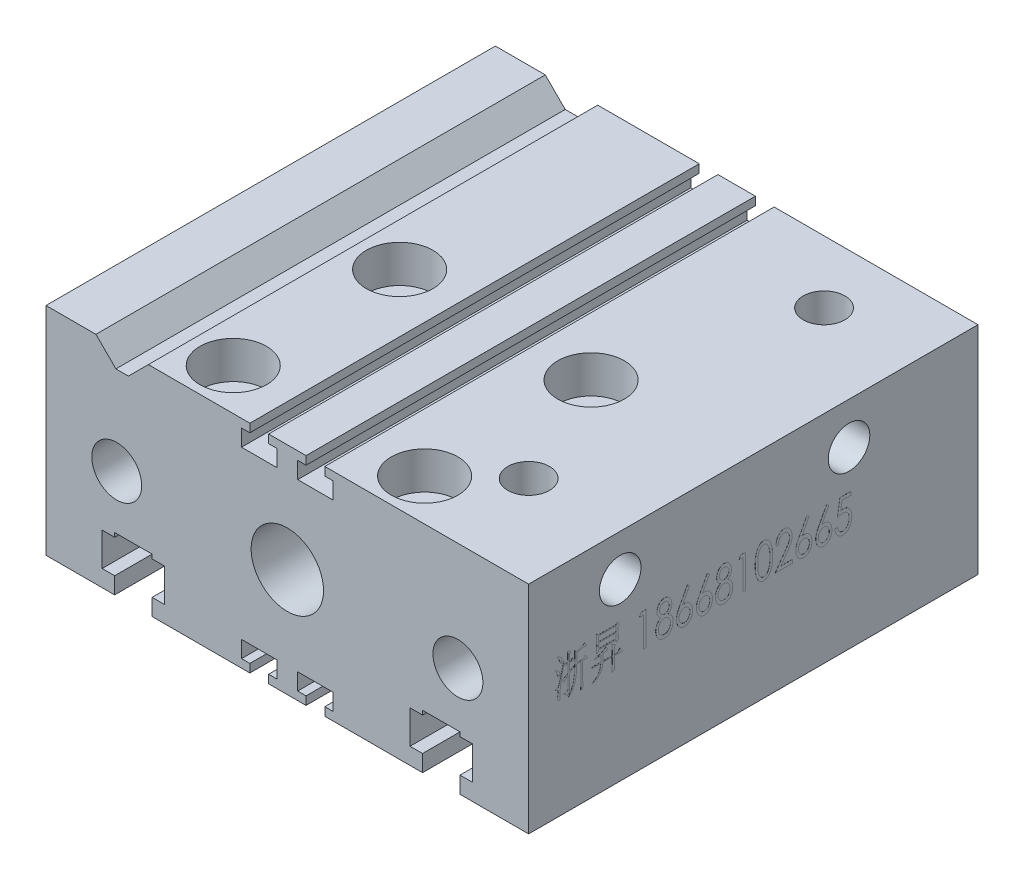
SolidWorks part; units mm, degrees
ref_plane "前视基准面" through (0, 0, 0) normal (0, 0, 1) x (1, 0, 0)
ref_plane "上视基准面" through (0, 0, 0) normal (0, 1, 0) x (1, 0, 0)
ref_plane "右视基准面" through (0, 0, 0) normal (1, 0, 0) x (0, 0, -1)
sketch "草图1" plane through (0, 0, 0) normal (0, 1, 0) x (1, 0, 0)
  line L0 (0, 0) -> (0, 54) construction
  line L1 (-29, 54) -> (29, 54)
  line L2 (-29, 54) -> (-29, 0)
  line L3 (-29, 0) -> (29, 0)
  line L4 (29, 54) -> (29, 0)
  line L5 (-11.5, 0) -> (-11.5, 54) construction
  line L6 (18, 54) -> (18, 0) construction
  line L7 (4.35, 0) -> (4.35, -5)
  line L8 (-29, -5) -> (29, -5)
  line L9 (-29, -5) -> (-29, -13)
  line L10 (-29, -13) -> (29, -13)
  line L11 (29, -5) -> (29, -13)
  line L12 (29, 0) -> (71, 0)
  circle A0 centre (18, 46.5) radius 2.5
  point P4 (29, 25)
  point P8 (0, 25)
  point P11 (-11.5, 5)
  point P12 (-11.5, 25)
  point P15 (18, 46.5)
  point P16 (18, 11)
  point P19 (29, 11)
  point P20 (29, 13.5)
  point P21 (29, 38.5)
  point P28 (0, 51)
  point P29 (0, 48)
  point P30 (-11.5, 15)
  point P31 (18, 54)
  point P33 (-11.5, 44)
  dimension "D2" = 38.5
  dimension "P" = 5
  dimension "D1" = 54
  dimension "B" = 58
  dimension "AC" = 29
  dimension "行程" = 25
  dimension "KB" = 23
  dimension "MB" = 5
  dimension "MC" = 20
  dimension "PB" = 18
  dimension "PD" = 11
  dimension "PF" = 7.5
  dimension "PC" = 11
  dimension "PE" = 13.5
  dimension "D3" = 8.7
  dimension "AD" = 8
  dimension "AB" = 13
  dimension "D4" = 67
  dimension "JA" = 3
  dimension "KA" = 6
  dimension "KC" = 15
  dimension "A" = 42
  dimension "LA" = 10
sketch "草图2" plane through (0, 0, 0) normal (0, 0, 1) x (1, 0, 0)
  line L0 (-29, 0) -> (0, 0) construction
  line L1 (-29, 13) -> (29, 13)
  line L2 (-29, 13) -> (-29, -13)
  line L3 (-29, -13) -> (-20.75, -13)
  line L4 (29, 13) -> (29, -13)
  line L5 (-29, 0) -> (29, 0) construction
  line L6 (0, 0) -> (0, 13) construction
  line L7 (-11.5, 13) -> (-11.5, -13) construction
  line L8 (-7.5, 13) -> (-7.5, 8.5)
  line L9 (-7.5, 8.5) -> (-9.25, 8.5)
  line L10 (-9.25, 8.5) -> (-9.25, -13)
  line L11 (29, 8) -> (24, 8)
  line L12 (-29, 0) -> (29, 0) construction
  line L13 (-11.75, 0) -> (-11.25, 0) construction
  line L14 (-11.75, 1.5) -> (-11.25, 1.5)
  line L15 (-11.75, -1.5) -> (-11.25, -1.5)
  line L16 (-9.25, -3) -> (-9, -3)
  line L17 (-2.25, -13) -> (-2.25, -12)
  line L18 (-9, -3) -> (-9, -13)
  line L19 (-4.5, -12) -> (-4.5, -13)
  line L20 (-16.25, -13) -> (-16.25, -11)
  line L21 (-16.25, -11) -> (-14.75, -11)
  line L22 (-14.75, -11) -> (-14.75, -7)
  line L23 (-14.75, -7) -> (-16.25, -7)
  line L24 (-22.25, -7) -> (-22.25, -11)
  line L25 (-22.25, -11) -> (-20.75, -11)
  line L26 (-20.75, -11) -> (-20.75, -13)
  line L27 (-23, 13) -> (-20.6, 10.6)
  line L28 (-20.6, 10.6) -> (-19.1, 10.6)
  line L29 (-19.1, 10.6) -> (-16.7, 13)
  line L36 (-20.75, -7) -> (-22.25, -7)
  line L37 (-20.75, -6.5) -> (-16.25, -6.5)
  line L38 (-20.75, -6.5) -> (-20.75, -7)
  line L39 (-16.25, -13) -> (29, -13)
  line L40 (-16.25, -6.5) -> (-16.25, -7)
  line L41 (-20.75, -13) -> (-16.25, -13) construction
  line L42 (-2.25, -12) -> (-1.25, -12)
  line L43 (-5.5, -10) -> (-1.25, -10)
  line L44 (-5.5, -10) -> (-5.5, -12)
  line L45 (-5.5, -12) -> (-4.5, -12)
  line L46 (-1.25, -10) -> (-1.25, -12)
  circle A0 centre (-20.5, 0) radius 3
  circle A1 centre (20.5, 0) radius 3
  circle A2 centre (-25, 9) radius 2
  circle A3 centre (-25, -9) radius 2
  circle A4 centre (11.5, 0) radius 1.5
  arc A5 (-11.75, 1.5) -> (-11.75, -1.5) centre (-11.75, 0) ccw
  arc A6 (-11.25, -1.5) -> (-11.25, 1.5) centre (-11.25, 0) ccw
  point P48 (-11.5, 0)
  point P52 (-18.5, -13)
  point P64 (-9.75, 0)
  point P65 (-13.25, 0)
  dimension "D1" = 1
  dimension "D" = 6
  dimension "D7" = 10.4
  dimension "L" = 4
  dimension "D10" = 2.4
  dimension "K" = 3
  dimension "C" = 26
  dimension "G" = 41
  dimension "U" = 7.5
  dimension "W" = 4
  dimension "V" = 4.5
  dimension "X" = 2
  dimension "Y" = 6.5
  dimension "S" = 37
  dimension "D2" = 1
  dimension "D3" = 2
  dimension "M" = 8
  dimension "MA" = 4.5
  dimension "N" = 4.5
  dimension "D4" = 2.25
  dimension "D5" = 2
  dimension "D6" = 135
  dimension "LC" = 18
  dimension "LB" = 50
  dimension "D8" = 2
  dimension "D9" = 5
  dimension "PA" = 8
  dimension "J" = 3.5
  dimension "R" = 5
  dimension "RA" = 10
sketch "草图3" plane through (0, 0, 0) normal (0, 0, 1) x (1, 0, 0)
  line L0 (0, 11) -> (0, 0) construction
  line L1 (-28, 11) -> (28, 11)
  line L2 (-28, 11) -> (-28, -11)
  line L3 (-28, -11) -> (28, -11)
  line L4 (28, 11) -> (28, -11)
  line L5 (-29, 0) -> (29, 0) construction
  line L6 (0, 0) -> (0, -11) construction
  line L7 (-29, 0) -> (29, 0) construction
  circle A0 centre (-24, 7) radius 2
  circle A1 centre (-25, 9) radius 2 construction
  dimension "BA" = 56
  dimension "CA" = 22
  dimension "LD" = 48
  dimension "LE" = 14
sketch "草图4" plane through (0, 0, 0) normal (0, 0, 1) x (1, 0, 0)
  line L0 (-14.75, -7) -> (-16.25, -7) construction
  line L1 (-14.75, -11) -> (-14.75, -7) construction
  line L2 (-16.25, -11) -> (-14.75, -11) construction
  line L3 (-16.25, -13) -> (-16.25, -11) construction
  line L4 (-16.25, -13) -> (29, -13) construction
  line L6 (-29, 13) -> (29, 13) construction
  line L7 (-29, 13) -> (-29, -13) construction
  line L8 (-29, -13) -> (-20.75, -13) construction
  line L9 (-20.75, -11) -> (-20.75, -13) construction
  line L10 (-22.25, -11) -> (-20.75, -11) construction
  line L11 (-22.25, -7) -> (-22.25, -11) construction
  line L12 (-20.75, -7) -> (-22.25, -7) construction
  line L13 (-20.75, -6.5) -> (-20.75, -7) construction
  line L14 (-20.75, -6.5) -> (-16.25, -6.5) construction
  line L15 (-16.25, -6.5) -> (-16.25, -7) construction
  line L26 (-23, 13) -> (-20.6, 10.6) construction
  line L27 (-20.6, 10.6) -> (-19.1, 10.6) construction
  line L28 (-19.1, 10.6) -> (-16.7, 13) construction
  line L29 (-14.75, -7) -> (-16.25, -7)
  line L30 (-14.75, -11) -> (-14.75, -7)
  line L31 (-16.25, -11) -> (-14.75, -11)
  line L32 (-16.25, -13) -> (-16.25, -11)
  line L33 (-16.25, -13) -> (0, -13)
  line L35 (-29, 13) -> (-23, 13)
  line L36 (-29, 13) -> (-29, -13)
  line L37 (-29, -13) -> (-20.75, -13)
  line L38 (-20.75, -11) -> (-20.75, -13)
  line L39 (-22.25, -11) -> (-20.75, -11)
  line L40 (-22.25, -7) -> (-22.25, -11)
  line L41 (-20.75, -7) -> (-22.25, -7)
  line L42 (-20.75, -6.5) -> (-20.75, -7)
  line L43 (-20.75, -6.5) -> (-16.25, -6.5)
  line L44 (-16.25, -6.5) -> (-16.25, -7)
  line L45 (0, 13) -> (0, -13)
  line L52 (-16.7, 13) -> (0, 13)
  line L55 (-23, 13) -> (-20.6, 10.6)
  line L56 (-20.6, 10.6) -> (-19.1, 10.6)
  line L57 (-19.1, 10.6) -> (-16.7, 13)
  circle A4 centre (-20.5, 0) radius 3 construction
  circle A5 centre (-20.5, 0) radius 3
extrude "凸台-拉伸1" add sketch "草图4" against normal up to vertex (54 mm away) up to point (0, 0, -54)
sketch "草图5" plane through (0, 0, 0) normal (0, 0, 1) x (1, 0, 0)
  line L0 (-5.5, -12) -> (-4.5, -12) construction
  line L1 (-4.5, -12) -> (-4.5, -13) construction
  line L2 (-5.5, -10) -> (-5.5, -12) construction
  line L3 (-5.5, -10) -> (-1.25, -10) construction
  line L4 (-1.25, -10) -> (-1.25, -12) construction
  line L5 (-2.25, -12) -> (-1.25, -12) construction
  line L6 (-2.25, -13) -> (-2.25, -12) construction
  line L7 (-5.5, -12) -> (-4.5, -12)
  line L8 (-4.5, -12) -> (-4.5, -13)
  line L9 (-5.5, -10) -> (-5.5, -12)
  line L10 (-5.5, -10) -> (-1.25, -10)
  line L11 (-1.25, -10) -> (-1.25, -12)
  line L12 (-2.25, -12) -> (-1.25, -12)
  line L13 (-2.25, -13) -> (-2.25, -12)
  line L14 (-4.5, -13) -> (-2.25, -13)
extrude "切除-拉伸1" cut sketch "草图5" against normal through all
mirror "镜向1" about plane through (0, 0, 0) normal (0, 1, 0) of "切除-拉伸1"
sketch "草图6" plane through (0, 13, 0) normal (0, 1, 0) x (-1, 0, 0)
  circle A0 centre (11.5, -25) radius 4
  circle A1 centre (11.5, -5) radius 4
  point P6 (7.5, -5)
extrude "切除-拉伸2" cut sketch "草图6" against normal up to vertex (4.5 mm away) up to point (-7.5, 8.5, 0)
sketch "草图7" plane through (0, 8.5, 0) normal (0, 1, 0) x (1, 0, 0)
  circle A0 centre (-11.5, 25) radius 2.25
  circle A1 centre (-11.5, 5) radius 2.25
  point P6 (-9.25, 25)
extrude "切除-拉伸3" cut sketch "草图7" against normal up to vertex (21.5 mm away) up to point (-9.25, -13, 0)
mirror "镜向2" about plane through (0, 0, 0) normal (1, 0, 0) of bodies 105
sketch "草图8" plane through (0, 0, 0) normal (0, 0, 1) x (1, 0, 0)
  line L0 (16.7, 13) -> (23, 13)
  line L1 (23, 13) -> (20.6, 10.6)
  line L2 (20.6, 10.6) -> (19.1, 10.6)
  line L3 (19.1, 10.6) -> (16.7, 13)
extrude "凸台-拉伸2" add sketch "草图8" against normal up to surface (54 mm away) up to face at (-17.5, 0, -54)
sketch "草图9" plane through (0, 13, 0) normal (0, 1, 0) x (1, 0, 0)
  circle A0 centre (18, 46.5) radius 2.5
  circle A1 centre (18, 11) radius 2.5
  circle A2 centre (18, 46.5) radius 2.5 construction
extrude "切除-拉伸4" cut sketch "草图9" against normal blind 5
sketch "草图10" plane through (29, 0, 0) normal (1, 0, 0) x (0, 0, -1)
  circle A0 centre (11, 8) radius 2.5
  circle A1 centre (38.5, 8) radius 2.5
  dimension "D1" = 5
extrude "切除-拉伸5" cut sketch "草图10" against normal up to vertex (5 mm away) up to point (24, 8, 0)
sketch "草图11" plane through (0, 0, 0) normal (0, 0, 1) x (1, 0, 0)
  line L0 (-29, 0) -> (29, 0) construction
  circle A0 centre (0, 0) radius 4.35
extrude "切除-拉伸6" cut sketch "草图11" against normal up to vertex (46.5 mm away) up to point (18, 0, -46.5)
sketch "草图12" plane through (0, 0, -54) normal (0, 0, -1) x (-1, 0, 0)
  line L0 (11.75, 1.5) -> (11.25, 1.5) construction
  line L1 (11.75, -1.5) -> (11.25, -1.5) construction
  line L2 (11.75, 1.5) -> (11.25, 1.5)
  line L3 (11.75, -1.5) -> (11.25, -1.5)
  circle A0 centre (-11.5, 0) radius 1.5 construction
  arc A1 (11.75, -1.5) -> (11.75, 1.5) centre (11.75, 0) ccw construction
  arc A2 (11.25, 1.5) -> (11.25, -1.5) centre (11.25, 0) ccw construction
  circle A3 centre (-11.5, 0) radius 1.5
  arc A4 (11.75, -1.5) -> (11.75, 1.5) centre (11.75, 0) ccw
  arc A5 (11.25, 1.5) -> (11.25, -1.5) centre (11.25, 0) ccw
extrude "切除-拉伸7" cut sketch "草图12" against normal up to vertex (3 mm away) up to point (0, 0, -51)
sketch "草图13" plane through (0, 0, -51) normal (0, 0, -1) x (-1, 0, 0)
  line L0 (11.5, 13) -> (11.5, -13) construction
  circle A0 centre (11.5, 0) radius 1.5
  circle A2 centre (-11.5, 0) radius 1.5
  circle A3 centre (-11.5, 0) radius 1.5
  dimension "D1" = 0
extrude "凸台-拉伸4" add sketch "草图13" against normal up to vertex (3 mm away) up to point (0, 0, -48)
sketch "草图14" plane through (0, -13, 0) normal (0, -1, 0) x (1, 0, 0)
  circle A0 centre (-11.5, -15) radius 1.5
  circle A1 centre (11.5, -15) radius 1.5
  dimension "D1" = 3
extrude "切除-拉伸8" cut sketch "草图14" against normal blind 6
sketch "草图15" plane through (0, -13, 0) normal (0, -1, 0) x (1, 0, 0)
  line L0 (-11.75, -15) -> (-11.25, -15) construction
  line L1 (-11.75, -13.5) -> (-11.25, -13.5)
  line L2 (-11.75, -16.5) -> (-11.25, -16.5)
  arc A0 (-11.75, -13.5) -> (-11.75, -16.5) centre (-11.75, -15) ccw
  arc A1 (-11.25, -16.5) -> (-11.25, -13.5) centre (-11.25, -15) ccw
  point P2 (-11.5, -15)
  point P7 (-9.75, -15)
  point P8 (-13.25, -15)
  dimension "D1" = 3.5
  dimension "D2" = 1.5
extrude "切除-拉伸9" cut sketch "草图15" against normal blind 3
sketch "草图16" plane through (0, 0, 0) normal (0, 0, 1) x (1, 0, 0)
  line L0 (-28, 11) -> (28, 11) construction
  line L1 (28, 11) -> (28, -11) construction
  line L2 (-28, -11) -> (28, -11) construction
  line L3 (-28, 11) -> (-28, -11) construction
  line L4 (-28, 11) -> (28, 11)
  line L5 (28, 11) -> (28, -11)
  line L6 (-28, -11) -> (28, -11)
  line L7 (-28, 11) -> (-28, -11)
extrude "凸台-拉伸5" add sketch "草图16" along normal up to vertex (13 mm away) from vertex separate body up to point (29, 0, 13) starting at point (29, 0, 5)
sketch "草图18" plane through (0, 0, 13) normal (0, 0, 1) x (1, 0, 0)
  circle A0 centre (20.5, 0) radius 3 construction
  circle A1 centre (-20.5, 0) radius 3 construction
  circle A2 centre (20.5, 0) radius 3
  circle A3 centre (-20.5, 0) radius 3
extrude "凸台-拉伸6" add sketch "草图18" against normal up to vertex (67 mm away) up to point (18, 0, -54)
sketch "草图19" plane through (0, 0, 13) normal (0, 0, 1) x (1, 0, 0)
  circle A0 centre (0, 0) radius 4.35
extrude "凸台-拉伸7" add sketch "草图19" against normal up to vertex (59.5 mm away) up to point (18, 0, -46.5)
sketch "草图20" plane through (0, 0, 13) normal (0, 0, 1) x (1, 0, 0)
  circle A0 centre (-24, 7) radius 2 construction
  circle A1 centre (-24, 7) radius 2
extrude "切除-拉伸10" cut sketch "草图20" against normal up to vertex (8 mm away) up to point (-29, 0, 5)
mirror "镜向3" about plane through (0, 0, 0) normal (0, 1, 0) of "切除-拉伸10"
mirror "镜向4" about plane through (0, 0, 0) normal (1, 0, 0) of "镜向3"
sketch "草图21" plane through (0, 0, 13) normal (0, 0, 1) x (1, 0, 0)
  line L0 (-11.75, 1.5) -> (-11.25, 1.5) construction
  line L1 (-11.75, -1.5) -> (-11.25, -1.5) construction
  line L2 (-11.75, 1.5) -> (-11.25, 1.5)
  line L3 (-11.75, -1.5) -> (-11.25, -1.5)
  circle A0 centre (11.5, 0) radius 1.5 construction
  arc A1 (-11.25, -1.5) -> (-11.25, 1.5) centre (-11.25, 0) ccw construction
  arc A2 (-11.75, 1.5) -> (-11.75, -1.5) centre (-11.75, 0) ccw construction
  circle A3 centre (11.5, 0) radius 1.5
  arc A4 (-11.25, -1.5) -> (-11.25, 1.5) centre (-11.25, 0) ccw
  arc A5 (-11.75, 1.5) -> (-11.75, -1.5) centre (-11.75, 0) ccw
extrude "切除-拉伸11" cut sketch "草图21" against normal blind 3
sketch "草图22" plane through (0, 0, 10) normal (0, 0, 1) x (1, 0, 0)
  circle A0 centre (-11.5, 0) radius 1.5
  circle A1 centre (11.5, 0) radius 1.5
  circle A2 centre (11.5, 0) radius 1.5
  dimension "D1" = 0
extrude "切除-拉伸12" cut sketch "草图22" against normal blind 3
sketch "草图23" plane through (0, 0, 0) normal (0, 1, 0) x (1, 0, 0)
  line L0 (0, 0) -> (0, -25)
  line L1 (-29, 0) -> (29, 0) construction
  line L2 (0, -25) -> (1, -25)
  line L3 (0, 0) -> (29, 0)
  dimension "D1" = 1
  dimension "D2" = 25
delete or keep bodies "实体-删除1" type delete bodies bodies 123
sketch "草图24" plane through (29, -8.2719, -81.7181) normal (1, 0, 0) x (0, 0, -1)
  line L0 (-78.7181, 13.7719) -> (-78.7181, 7.6052) construction
  line L1 (-27.7181, -4.7281) -> (-81.7181, -4.7281) construction
  line L2 (-78.7181, 7.6052) -> (-78.7181, 1.4385) construction
  line L3 (-78.7181, 1.4385) -> (-78.7181, -4.7281) construction
  line L4 (-78.7181, 7.6052) -> (-81.7181, 7.6052) construction
  line L5 (-81.7181, 21.2719) -> (-81.7181, -4.7281) construction
  line L9 (-78.7181, 7.6052) -> (-75.7181, 7.6052) construction
  circle A2 centre (-70.7181, 16.2719) radius 2.5 construction
  circle A3 centre (-70.7181, 16.2719) radius 2.5 construction
  text T0 "浙昇 18668102665" font "Century Gothic" height in points 15
  point P14 (-70.7181, 13.7719)
  dimension "D1" = 3
extrude "LOGO" add sketch "草图24" along normal blind 0.01
